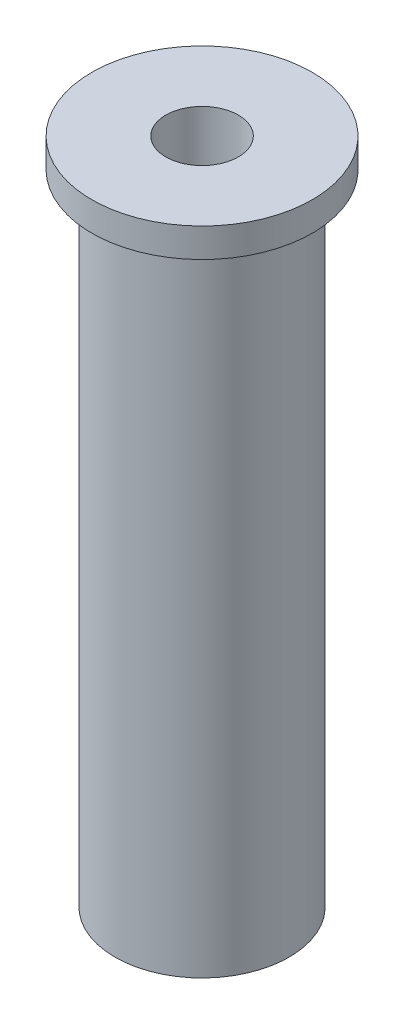
SolidWorks part; units mm, degrees
ref_plane "Front Plane" through (0, 0, 0) normal (0, 0, 1) x (1, 0, 0)
ref_plane "Top Plane" through (0, 0, 0) normal (0, 1, 0) x (1, 0, 0)
ref_plane "Right Plane" through (0, 0, 0) normal (1, 0, 0) x (0, 0, -1)
sketch "Sketch1" plane through (0, 0, 0) normal (1, 0, 0) x (0, 0, -1)
  line L0 (0, 0) -> (0, 12.3422) construction
  line L1 (1.25, 0) -> (1.25, 23)
  line L2 (1.25, 23) -> (3.8, 23)
  line L3 (3.8, 23) -> (3.8, 22)
  line L4 (3.8, 22) -> (3, 22)
  line L5 (3, 22) -> (3, 0)
  line L6 (3, 0) -> (1.25, 0)
  dimension "D1" = 1
  dimension "D2" = 22
  dimension "D3" = 1.25
  dimension "D4" = 3
  dimension "D5" = 3.8
revolve "Revolve1" add sketch "Sketch1" angle 360 about L0
